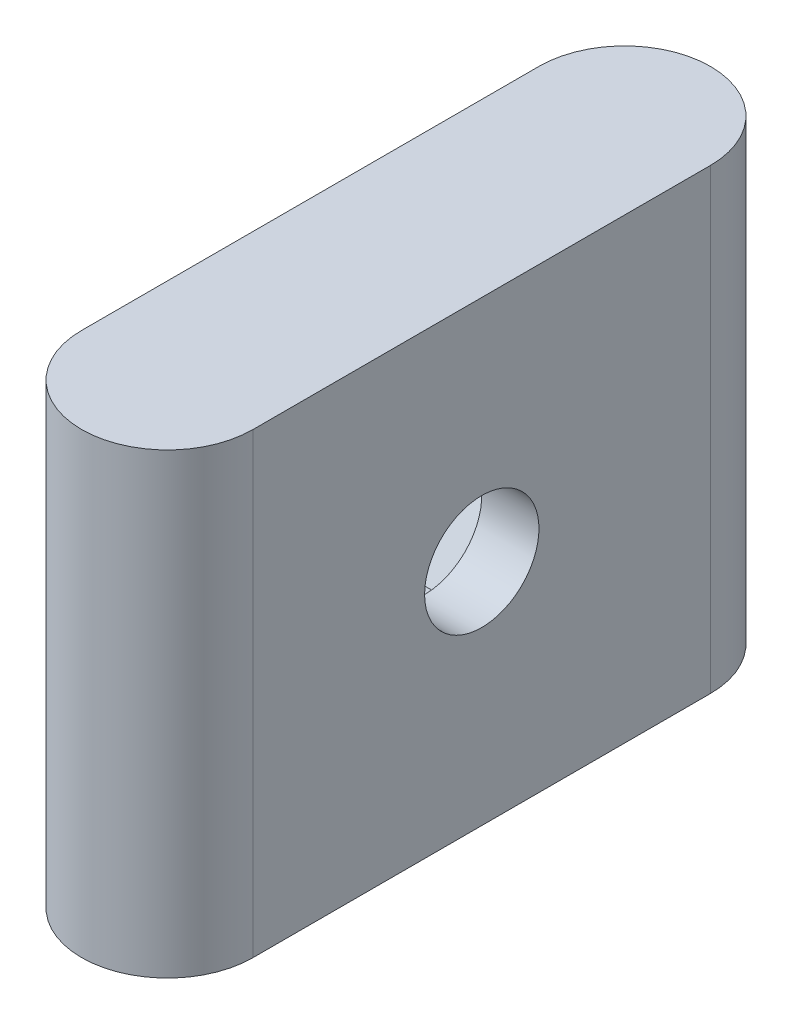
SolidWorks part; units mm, degrees
ref_plane "Front Plane" through (0, 0, 0) normal (0, 0, 1) x (1, 0, 0)
ref_plane "Top Plane" through (0, 0, 0) normal (0, 1, 0) x (1, 0, 0)
ref_plane "Right Plane" through (0, 0, 0) normal (1, 0, 0) x (0, 0, -1)
sketch "Sketch1" plane through (0, 0, 0) normal (0, 1, 0) x (1, 0, 0)
  line L0 (0, -8.4573) -> (0, 11.5427) construction
  line L1 (-3.75, -8.4573) -> (-3.75, 11.5427)
  line L2 (3.75, -8.4573) -> (3.75, 11.5427)
  arc A0 (-3.75, -8.4573) -> (3.75, -8.4573) centre (0, -8.4573) ccw
  arc A1 (3.75, 11.5427) -> (-3.75, 11.5427) centre (0, 11.5427) ccw
  point P3 (0, 1.5427)
  dimension "D1" = 7.5
  dimension "D2" = 20
extrude "Boss-Extrude1" add sketch "Sketch1" along normal blind 20
sketch "Sketch2" plane through (-3.75, 0, 0) normal (-1, 0, 0) x (0, 0, 1)
  line L0 (-11.5427, 10) -> (8.4573, 10) construction
  line L1 (-11.5427, 20) -> (-11.5427, 0) construction
  line L2 (8.4573, 20) -> (8.4573, 0) construction
  line L8 (4.4021, 10) -> (1.4297, 15.1483)
  line L9 (1.4297, 15.1483) -> (-4.5151, 15.1483)
  line L10 (-4.5151, 15.1483) -> (-7.4875, 10)
  line L11 (-7.4875, 10) -> (-4.5151, 4.8517)
  line L12 (-4.5151, 4.8517) -> (1.4297, 4.8517)
  line L13 (1.4297, 4.8517) -> (4.4021, 10)
  circle A0 centre (-1.5427, 10) radius 2.5
  circle A1 centre (-1.5427, 10) radius 5.1483 construction
  point P8 (4.4021, 10)
extrude "Cut-Extrude1" cut sketch "Sketch2" against normal blind 20 contours A0 region at (-3.75, 10, -1.5427)
extrude "Cut-Extrude2" cut sketch "Sketch2<4>" against normal blind 5
sketch "Sketch2<4>" plane through (-3.75, 0, 0) normal (-1, 0, 0) x (0, 0, 1) same geometry as "Sketch2"
